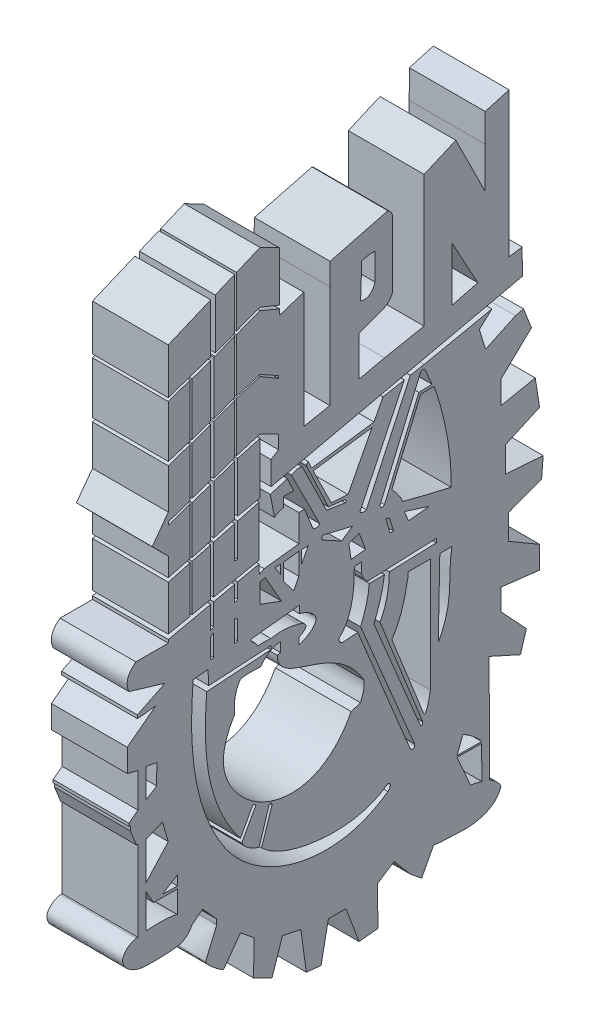
SolidWorks part; units mm, degrees
ref_plane "Alzado" through (0, 0, 0) normal (0, 0, 1) x (1, 0, 0)
ref_plane "Planta" through (0, 0, 0) normal (0, 1, 0) x (1, 0, 0)
ref_plane "Vista lateral" through (0, 0, 0) normal (1, 0, 0) x (0, 0, -1)
sketch "Croquis1" plane through (0, 0, 0) normal (1, 0, 0) x (0, 0, -1)
  line L0 (43.9363, 412.25) -> (43.9363, 221.2356)
  line L1 (43.9363, 221.2356) -> (23.5887, 211.0722)
  line L2 (23.5887, 211.0722) -> (23.5887, 208.8989)
  line L3 (16.8721, 195.9684) -> (35.5368, 210.1775)
  line L4 (23.9312, 137.0973) -> (23.9312, 156.5149)
  line L5 (23.9312, 179.1342) -> (23.9312, 197.7161)
  line L6 (16.8721, 195.9684) -> (16.8721, 180.9324)
  line L7 (16.8721, 180.9324) -> (23.9312, 179.1342)
  line L8 (23.9312, 179.1342) -> (23.9312, 156.5149)
  line L9 (23.9312, 156.5149) -> (17.9978, 151.9978)
  line L10 (17.9978, 151.9978) -> (17.9978, 150.0739)
  line L11 (17.9978, 150.0739) -> (18.9598, 150.0739)
  line L12 (18.9598, 150.0739) -> (18.9598, 147.1462)
  line L13 (18.9598, 147.1462) -> (22.9471, 137.0973)
  line L14 (22.9471, 137.0973) -> (23.9312, 137.0973)
  line L15 (23.9312, 137.0973) -> (23.9312, 83.8311)
  line L16 (23.9312, 83.8311) -> (22.9471, 83.8311)
  line L17 (56.0134, 68.3425) -> (75.8715, 68.3425)
  line L18 (75.8715, 68.3425) -> (75.8715, 65.2167)
  line L19 (263.3658, 283.0745) -> (283.4663, 271.8939)
  line L20 (263.3658, 283.0745) -> (263.3658, 267.8402)
  line L21 (263.3658, 267.8402) -> (285.9583, 272.3965)
  line L22 (285.9583, 272.3965) -> (309.7108, 262.7097)
  line L23 (309.7108, 262.7097) -> (310.5308, 247.9633)
  line L24 (310.5308, 247.9633) -> (288.8511, 254.1537)
  line L25 (288.8511, 254.1537) -> (285.9583, 272.3965)
  line L26 (287.5429, 272.8731) -> (285.9583, 272.3965)
  line L27 (288.8511, 254.1537) -> (266.2176, 243.9811)
  line L28 (266.2176, 243.9811) -> (266.2176, 227.2088)
  line L29 (266.2176, 227.2088) -> (291.2115, 225.4)
  line L30 (291.2115, 225.4) -> (291.2115, 235.5949)
  line L31 (291.2115, 235.5949) -> (266.2176, 243.9811)
  line L32 (291.2115, 235.5949) -> (310.5308, 247.9633)
  line L33 (268.337, 204.3163) -> (290.1487, 199.5858)
  line L34 (290.1487, 199.5858) -> (310.5308, 204.7917)
  line L35 (310.5308, 204.7917) -> (290.1487, 212.4724)
  line L36 (290.1487, 212.4724) -> (268.337, 204.3163)
  line L37 (290.1487, 212.4724) -> (291.2115, 225.4)
  line L38 (291.2115, 225.4) -> (310.5308, 218.9362)
  line L39 (310.5308, 218.9362) -> (310.5308, 204.7917)
  line L40 (268.337, 204.3163) -> (268.337, 187.8388)
  line L41 (268.337, 187.8388) -> (290.1487, 184.8338)
  line L42 (290.1487, 184.8338) -> (290.1487, 199.5858)
  line L43 (268.337, 187.8388) -> (288.8511, 175.8962)
  line L44 (288.8511, 175.8962) -> (309.7108, 172.2125)
  line L45 (309.7108, 172.2125) -> (290.1487, 184.8338)
  line L46 (288.8511, 175.8962) -> (288.8511, 161.1612)
  line L47 (288.8511, 161.1612) -> (309.7108, 159.5496)
  line L48 (309.7108, 159.5496) -> (309.7108, 172.2125)
  line L49 (263.3658, 164.1543) -> (288.8511, 161.1612)
  line L50 (263.3658, 164.1543) -> (263.3658, 150.0739)
  line L51 (263.3658, 150.0739) -> (283.4663, 148.3805)
  line L52 (283.4663, 148.3805) -> (285.0201, 161.6111)
  line L53 (263.3658, 150.0739) -> (280.1263, 132.1)
  line L54 (280.1263, 132.1) -> (299.2809, 130.6201)
  line L55 (299.2809, 130.6201) -> (283.4663, 148.3805)
  line L56 (280.1263, 132.1) -> (276.1921, 119.1503)
  line L57 (276.1921, 119.1503) -> (297.642, 119.1503)
  line L58 (297.642, 119.1503) -> (299.2809, 130.6201)
  line L59 (276.1921, 119.1503) -> (255.4875, 128.5526)
  line L60 (255.4875, 128.5526) -> (255.4875, 114.8521)
  line L61 (255.4875, 114.8521) -> (276.1921, 114.8521)
  line L62 (276.1921, 114.8521) -> (276.1921, 119.1503)
  line L63 (276.1921, 114.8521) -> (285.9583, 90.7476)
  line L64 (285.9583, 90.7476) -> (265.8398, 90.7476)
  line L65 (265.8398, 90.7476) -> (255.4875, 107.5904)
  line L66 (255.4875, 107.5904) -> (255.4875, 114.8521)
  line L67 (265.8398, 90.7476) -> (261.683, 78.6554)
  line L68 (261.683, 78.6554) -> (276.1921, 78.6554)
  line L69 (276.1921, 78.6554) -> (285.9583, 90.7476)
  line L70 (191.9441, 411.0372) -> (191.9441, 368.61)
  line L71 (183.7002, 361.1306) -> (169.7452, 356.0931)
  line L72 (169.7452, 356.0931) -> (186.6079, 346.5612)
  line L73 (169.7452, 356.0931) -> (169.7452, 329.7434)
  line L74 (169.7452, 329.7434) -> (186.5364, 333.5356)
  line L75 (233.601, 434.3151) -> (252.8256, 395.6782)
  line L76 (252.8256, 395.6782) -> (252.8256, 422.5142)
  line L77 (230.9785, 377.0491) -> (230.9785, 341.2878)
  line L78 (230.9785, 341.2878) -> (248.1079, 345.686)
  line L79 (248.1079, 345.686) -> (230.9785, 377.0491)
  line L80 (268.7154, 445.594) -> (268.7154, 350.1414)
  line L81 (268.7154, 350.1414) -> (277.3331, 351.5101)
  line L82 (276.1921, 317.421) -> (257.3854, 326.0513)
  line L83 (257.3854, 326.0513) -> (249.065, 318.4242)
  line L84 (249.065, 318.4242) -> (253.2252, 305.1547)
  line L85 (253.2252, 305.1547) -> (272.9115, 314.4257)
  line L86 (257.3854, 326.0513) -> (212.6544, 316.7428)
  line L87 (277.4757, 334.6795) -> (111.7206, 297.3389)
  line L88 (111.7206, 297.3389) -> (111.7206, 312.8594)
  line L89 (111.7206, 312.8594) -> (116.6334, 315.9908)
  line L90 (116.6334, 315.9908) -> (116.6334, 392.1998)
  line L91 (116.6334, 392.1998) -> (133.289, 397.6851)
  line L92 (133.289, 397.6851) -> (133.289, 320.9599)
  line L93 (133.289, 320.9599) -> (150.5326, 324.3307)
  line L94 (150.5326, 324.3307) -> (150.5326, 392.1998)
  line L95 (145.3173, 393.7699) -> (133.289, 397.6851)
  line L96 (261.683, 78.6554) -> (265.8398, 55.7232)
  line L97 (265.8398, 55.7232) -> (263.3658, 50.7772)
  line L98 (211.0187, 24.1224) -> (231.7393, 24.1224)
  line L99 (43.9363, 316.7428) -> (33.362, 302.302)
  line L100 (33.362, 302.302) -> (43.9363, 291.6046)
  line L101 (43.9363, 277.8816) -> (23.5887, 277.8816)
  line L102 (22.5389, 265.6648) -> (43.9363, 252.0848)
  line L103 (43.9363, 241.8738) -> (22.5389, 241.8738)
  line L104 (29.0853, 84.89) -> (29.0853, 199.5182)
  line L105 (29.0853, 199.5182) -> (39.1615, 209.0544)
  line L106 (39.1615, 209.0544) -> (50.0064, 197.5953)
  line L107 (50.0064, 197.5953) -> (50.0064, 83.8411)
  line L108 (54.1542, 81.4316) -> (54.1542, 197.5686)
  line L109 (54.1542, 197.5686) -> (42.739, 210.9483)
  line L110 (43.9363, 221.2356) -> (107.169, 252.7809)
  line L111 (107.169, 252.7809) -> (142.7909, 257.1439)
  line L113 (239.3484, 231.9879) -> (23.5887, 208.8989)
  line L114 (23.9312, 197.7161) -> (35.5368, 210.1775)
  line L115 (226.2809, 233.3335) -> (174.6192, 247.0102)
  line L116 (174.6192, 247.0102) -> (132.3561, 224.2069)
  line L117 (132.3561, 224.2069) -> (226.2809, 233.3335)
  line L118 (170.7616, 247.9633) -> (130.0415, 224.807)
  line L119 (130.0415, 224.807) -> (144.7007, 255.0685)
  line L120 (144.7007, 255.0685) -> (170.7616, 247.9633)
  line L121 (139.4645, 254.1537) -> (126.6124, 225.4)
  line L122 (126.6124, 225.4) -> (111.7206, 250.6964)
  line L123 (111.7206, 250.6964) -> (139.4645, 254.1537)
  line L124 (108.3015, 250.7703) -> (123.3251, 225.4)
  line L125 (85.7924, 238.6401) -> (123.3251, 225.4)
  line L126 (40.071, 215.5607) -> (80.3506, 236.3501)
  line L127 (80.3506, 236.3501) -> (119.9214, 222.7661)
  line L128 (119.9214, 222.7661) -> (40.071, 215.5607)
  line L129 (231.7393, 24.1224) -> (238.2993, 37.8143)
  line L130 (211.0187, 24.1224) -> (218.9341, 39.023)
  line L131 (88.9371, 431.138) -> (88.9371, 397.6851)
  line L132 (88.9371, 397.6851) -> (104.4667, 403.5146)
  line L133 (104.4667, 403.5146) -> (104.4667, 437.6562)
  line L134 (74.9479, 425.2664) -> (74.9479, 392.1998)
  line L135 (74.9479, 392.1998) -> (87.7057, 396.9888)
  line L136 (87.7057, 396.9888) -> (87.7057, 430.6212)
  line L137 (43.9363, 382.0604) -> (71.8987, 391.5214)
  line L138 (71.8987, 391.5214) -> (71.8987, 423.9866)
  line L139 (43.9363, 379.9088) -> (58.3682, 385.0332)
  line L140 (58.3682, 385.0332) -> (58.3682, 350.1414)
  line L141 (58.3682, 350.1414) -> (43.9363, 345.686)
  line L142 (59.607, 385.0332) -> (59.607, 350.1414)
  line L143 (59.607, 350.1414) -> (71.8987, 354.8191)
  line L144 (71.8987, 354.8191) -> (71.8987, 389.2227)
  line L145 (71.8987, 389.2227) -> (59.607, 385.0332)
  line L146 (74.9479, 390.2226) -> (87.7057, 395.6782)
  line L147 (87.7057, 395.6782) -> (87.7057, 360.389)
  line L148 (87.7057, 360.389) -> (73.9528, 354.8191)
  line L149 (73.9528, 354.8191) -> (73.9528, 390.2226)
  line L150 (73.9528, 390.2226) -> (74.9479, 390.2226)
  line L151 (88.9371, 395.6782) -> (104.4667, 401.5078)
  line L152 (104.4667, 401.5078) -> (104.4667, 365.1049)
  line L153 (104.4667, 365.1049) -> (88.9371, 360.389)
  line L154 (88.9371, 360.389) -> (88.9371, 395.6782)
  line L155 (43.9363, 343.2284) -> (58.3682, 348.139)
  line L156 (58.3682, 348.139) -> (58.3682, 315.9908)
  line L157 (58.3682, 315.9908) -> (43.9363, 311.0802)
  line L158 (59.607, 348.139) -> (59.607, 316.7428)
  line L159 (59.607, 316.7428) -> (71.8987, 320.9599)
  line L160 (71.8987, 320.9599) -> (71.8987, 351.5101)
  line L161 (71.8987, 352.9352) -> (59.607, 348.139)
  line L162 (71.8987, 351.5101) -> (71.8987, 352.9352)
  line L163 (73.9528, 353.5583) -> (87.7268, 358.6971)
  line L164 (87.7268, 358.6971) -> (87.7268, 326.0591)
  line L165 (87.7268, 326.0591) -> (73.9528, 320.9203)
  line L166 (73.9528, 320.9203) -> (73.9528, 353.5583)
  line L167 (88.9371, 359.2056) -> (104.4667, 363.9511)
  line L168 (104.4667, 363.9511) -> (104.4667, 331.1308)
  line L169 (104.4667, 331.1308) -> (88.9371, 326.3853)
  line L170 (88.9371, 326.3853) -> (88.9371, 359.2056)
  line L171 (43.9363, 309.2621) -> (58.3682, 314.4257)
  line L172 (58.3682, 314.4257) -> (58.3682, 283.0745)
  line L173 (58.3682, 283.0745) -> (43.9363, 279.2604)
  line L174 (59.607, 314.4257) -> (71.8987, 318.4242)
  line L175 (71.8987, 318.4242) -> (71.8987, 286.9367)
  line L176 (59.607, 282.9382) -> (71.8987, 286.2245)
  line L177 (59.607, 282.9382) -> (59.607, 314.4257)
  line L178 (73.9528, 318.4242) -> (73.9528, 286.9367)
  line L179 (71.8987, 286.2245) -> (71.8987, 286.9367)
  line L180 (87.7268, 291.6118) -> (87.7268, 322.0786)
  line L181 (73.9528, 318.4242) -> (73.9528, 319.2123)
  line L182 (89.7282, 324.5491) -> (104.4667, 328.6171)
  line L183 (104.4667, 328.6171) -> (104.4667, 294.5937)
  line L184 (104.4667, 294.5937) -> (89.7282, 291.6118)
  line L185 (89.7282, 291.6118) -> (89.7282, 324.5491)
  line L186 (73.9528, 319.2123) -> (87.7268, 323.8874)
  line L187 (87.7268, 323.8874) -> (87.7268, 322.0786)
  line L188 (73.9528, 286.9367) -> (87.7268, 290.9366)
  line L189 (87.7268, 290.9366) -> (87.7268, 291.6118)
  line L190 (43.9363, 276.7135) -> (58.3682, 280.5166)
  line L191 (58.3682, 280.5166) -> (58.3682, 250.7703)
  line L192 (59.607, 280.8431) -> (59.607, 250.2453)
  line L193 (71.8987, 284.0822) -> (71.8987, 252.783)
  line L194 (73.9161, 284.6138) -> (73.9161, 253.1994)
  line L195 (87.7268, 288.2533) -> (87.7268, 266.9268)
  line L196 (87.7268, 266.9268) -> (89.7282, 266.9268)
  line L197 (89.7282, 266.9268) -> (89.7282, 288.7807)
  line L198 (89.7282, 288.7807) -> (103.8958, 292.5142)
  line L199 (73.9161, 284.6138) -> (87.7268, 288.2533)
  line L200 (59.607, 280.8431) -> (71.8987, 284.0822)
  line L201 (43.9363, 247.0102) -> (58.3682, 249.9896)
  line L202 (103.8958, 259.3887) -> (103.8958, 292.5142)
  line L203 (73.9161, 253.1994) -> (103.8958, 259.3887)
  line L204 (58.3682, 250.7703) -> (58.3682, 249.9896)
  line L205 (59.607, 250.2453) -> (71.8987, 252.783)
  line L206 (43.9363, 243.9811) -> (71.8987, 250.1196)
  line L207 (71.8987, 250.1196) -> (71.8987, 235.1854)
  line L208 (73.9161, 250.5625) -> (73.9161, 236.1918)
  line L209 (87.7268, 253.5944) -> (87.7268, 243.0816)
  line L210 (89.7282, 254.0337) -> (89.7282, 244.0801)
  line L211 (89.7282, 254.0337) -> (103.8958, 257.1439)
  line L212 (73.9161, 250.5625) -> (87.7268, 253.5944)
  line L213 (114.2618, 249.7709) -> (117.9329, 244.0801)
  line L214 (117.9329, 244.0801) -> (117.9329, 250.1196)
  line L215 (117.9329, 250.1196) -> (114.2618, 249.7709)
  line L216 (119.9214, 250.1196) -> (130.0415, 251.3807)
  line L217 (130.0415, 251.3807) -> (130.0415, 237.048)
  line L218 (130.0415, 237.048) -> (126.6124, 230.4015)
  line L219 (126.6124, 230.4015) -> (119.9214, 239.2883)
  line L220 (119.9214, 239.2883) -> (119.9214, 250.1196)
  line L221 (131.8859, 251.3807) -> (136.2774, 251.3807)
  line L222 (136.2774, 251.3807) -> (131.8859, 243.0816)
  line L223 (131.8859, 243.0816) -> (131.8859, 251.3807)
  line L224 (71.8987, 231.9879) -> (71.8987, 218.4327)
  line L225 (73.9161, 233.0291) -> (73.9161, 218.6148)
  line L226 (87.7268, 233.818) -> (87.7268, 219.861)
  line L227 (89.7282, 233.131) -> (89.7282, 220.0416)
  line L228 (145.3173, 252.7809) -> (145.3173, 250.1196)
  line L229 (145.3173, 250.1196) -> (158.2073, 243.0816)
  line L230 (158.2073, 243.0816) -> (165.4522, 247.9633)
  line L231 (165.4522, 247.9633) -> (145.3173, 252.7809)
  line L232 (163.0364, 239.2883) -> (169.7452, 241.8738)
  line L233 (169.7452, 241.8738) -> (174.1664, 230.4015)
  line L234 (174.1664, 230.4015) -> (164.4859, 229.4093)
  line L235 (164.4859, 229.4093) -> (163.0364, 239.2883)
  line L236 (220.6941, 213.355) -> (220.6941, 210.7982)
  line L237 (220.6941, 210.7982) -> (189.7708, 209.748)
  line L238 (183.5235, 184.1455) -> (211.6828, 113.2795)
  line L239 (212.6544, 116.8748) -> (191.3534, 170.1599)
  line L240 (223.0228, 203.5582) -> (230.9785, 203.5582)
  line L241 (216.77, 200.5213) -> (216.77, 128.5526)
  line L242 (216.77, 200.5213) -> (216.77, 203.5582)
  line L243 (216.77, 203.5582) -> (202.0039, 203.5582)
  line L244 (202.0039, 203.5582) -> (202.0039, 200.5213)
  line L245 (223.0228, 203.5582) -> (221.9912, 152.8582)
  spline S0 degree 3 poles (22.9471, 83.8311) (19.2347, 83.6756) (13.3804, 79.0493) (14.3398, 69.9272) (21.2783, 66.0681) (29.6539, 64.546) (53.7403, 65.0523) (54.0322, 67.3359) (56.0134, 68.3425) knots 0 0 0 0 0.182088 0.2261 0.496742 0.557462 0.772579 1 1 1 1
  spline S1 degree 3 poles (75.8715, 65.2167) (75.7324, 63.7271) (71.8626, 56.1185) (69.0831, 49.2329) (67.7913, 45.7368) (77.8952, 38.3773) (80.3506, 37.1752) knots 0 0 0 0 0.597773 0.693632 0.735053 1 1 1 1
  spline S2 degree 1 poles (43.9363, 412.25) (104.4667, 437.6562) knots 0 0 1 1
  spline S3 degree 1 poles (104.4667, 437.6562) (145.6538, 416.4816) knots 0 0 1 1
  spline S4 degree 1 poles (145.6538, 416.4816) (145.3173, 393.7699) knots 0 0 1 1
  spline S5 degree 1 poles (145.3173, 393.7699) (150.5326, 392.1998) knots 0 0 1 1
  spline S6 degree 1 poles (150.5326, 392.1998) (150.6897, 406.6305) knots 0 0 1 1
  spline S7 degree 1 poles (150.6897, 406.6305) (188.7781, 416.4816) knots 0 0 1 1
  spline S8 degree 1 poles (188.7781, 416.4816) (208.7397, 405.4302) knots 0 0 1 1
  spline S9 degree 1 poles (208.7397, 405.4302) (208.8847, 361.1306) knots 0 0 1 1
  spline S10 degree 2 poles (208.8847, 361.1306) (201.2606, 348.0995) (186.6079, 346.5612) knots 0 0 0 1 1 1
  spline S11 degree 1 poles (186.6079, 346.5612) (186.5364, 333.5356) knots 0 0 1 1
  spline S12 degree 1 poles (186.5364, 333.5356) (212.6544, 338.6067) knots 0 0 1 1
  spline S13 degree 1 poles (212.6544, 338.6067) (212.6883, 425.2664) knots 0 0 1 1
  spline S14 degree 1 poles (212.6883, 425.2664) (233.601, 434.3151) knots 0 0 1 1
  spline S15 degree 1 poles (233.601, 434.3151) (252.8256, 422.5142) knots 0 0 1 1
  spline S16 degree 2 poles (23.5887, 277.8816) (20.6152, 272.0241) (22.5389, 265.6648) knots 0 0 0 1 1 1
  spline S17 degree 1 poles (252.8256, 422.5142) (252.9657, 441.0734) knots 0 0 1 1
  spline S18 degree 1 poles (252.9657, 441.0734) (268.7154, 445.594) knots 0 0 1 1
  spline S19 degree 1 poles (268.7154, 445.594) (287.3763, 433.6324) knots 0 0 1 1
  spline S20 degree 1 poles (287.3763, 433.6324) (287.5429, 345.686) knots 0 0 1 1
  spline S21 degree 1 poles (287.5429, 345.686) (297.5942, 338.6067) knots 0 0 1 1
  spline S22 degree 1 poles (297.5942, 338.6067) (297.642, 322.4637) knots 0 0 1 1
  spline S23 degree 1 poles (297.642, 322.4637) (276.1921, 317.421) knots 0 0 1 1
  spline S24 degree 1 poles (276.1921, 317.421) (272.9115, 314.4257) knots 0 0 1 1
  spline S25 degree 1 poles (272.9115, 314.4257) (278.1889, 315.7094) knots 0 0 1 1
  spline S26 degree 1 poles (278.1889, 315.7094) (283.4663, 302.302) knots 0 0 1 1
  spline S27 degree 1 poles (283.4663, 302.302) (305.289, 291.6046) knots 0 0 1 1
  spline S28 degree 1 poles (278.1889, 315.7094) (300.4395, 305.1547) knots 0 0 1 1
  spline S29 degree 1 poles (300.4395, 305.1547) (305.289, 291.6046) knots 0 0 1 1
  spline S30 degree 1 poles (277.3331, 351.5101) (277.4757, 334.6795) knots 0 0 1 1
  spline S31 degree 1 poles (277.4757, 334.6795) (297.642, 322.4637) knots 0 0 1 1
  spline S32 degree 1 poles (277.3331, 351.5101) (287.5429, 345.686) knots 0 0 1 1
  spline S33 degree 1 poles (283.4663, 302.302) (263.3658, 283.0745) knots 0 0 1 1
  spline S34 degree 1 poles (305.289, 291.6046) (287.5429, 272.8731) knots 0 0 1 1
  spline S35 degree 2 poles (188.7781, 416.4816) (191.8661, 414.5474) (191.9441, 411.0372) knots 0 0 0 1 1 1
  spline S36 degree 2 poles (191.9441, 368.61) (189.8169, 362.9706) (183.7002, 361.1306) knots 0 0 0 1 1 1
  spline S37 degree 2 poles (22.5389, 241.8738) (14.2242, 235.7793) (17.9978, 227.2088) knots 0 0 0 1 1 1
  spline S38 degree 1 poles (17.9978, 227.2088) (41.6864, 220.1118) knots 0 0 1 1
  spline S39 degree 1 poles (108.3015, 250.7703) (85.7924, 238.6401) knots 0 0 1 1
  spline S40 degree 1 poles (171.5383, 396.5308) (170.7616, 373.7786) knots 0 0 1 1
  spline S41 degree 1 poles (180.3799, 397.6851) (180.3799, 379.9088) knots 0 0 1 1
  spline S42 degree 2 poles (171.5383, 396.5308) (175.2223, 397.7159) (180.3799, 397.6851) knots 0 0 0 1 1 1
  spline S43 degree 2 poles (170.7616, 373.7786) (177.4327, 371.9515) (180.3799, 379.9088) knots 0 0 0 1 1 1
  spline S44 degree 1 poles (80.3506, 37.1752) (91.5252, 52.5778) knots 0 0 1 1
  spline S45 degree 1 poles (91.5252, 52.5778) (100.5968, 45.3651) knots 0 0 1 1
  spline S46 degree 1 poles (100.5968, 45.3651) (100.1325, 22.5345) knots 0 0 1 1
  spline S47 degree 1 poles (100.1325, 22.5345) (112.368, 16.5573) knots 0 0 1 1
  spline S48 degree 1 poles (250.6259, 45.3651) (255.9424, 48.4483) knots 0 0 1 1
  spline S49 degree 1 poles (112.368, 16.5573) (119.2574, 37.1693) knots 0 0 1 1
  spline S50 degree 1 poles (119.2574, 37.1693) (131.376, 34.6523) knots 0 0 1 1
  spline S51 degree 1 poles (131.376, 34.6523) (134.9432, 8.4052) knots 0 0 1 1
  spline S52 degree 1 poles (134.9432, 8.4052) (144.7007, 7.3621) knots 0 0 1 1
  spline S53 degree 1 poles (144.7007, 7.3621) (149.5454, 31.6408) knots 0 0 1 1
  spline S54 degree 1 poles (149.5454, 31.6408) (161.1653, 31.5963) knots 0 0 1 1
  spline S55 degree 1 poles (161.1653, 31.5963) (169.7452, 8.5201) knots 0 0 1 1
  spline S56 degree 1 poles (169.7452, 8.5201) (182.2725, 9.8027) knots 0 0 1 1
  spline S57 degree 1 poles (182.2725, 9.8027) (181.7957, 35.4223) knots 0 0 1 1
  spline S58 degree 1 poles (80.3506, 37.1752) (100.4302, 37.1693) knots 0 0 1 1
  spline S59 degree 2 poles (144.7007, 7.3621) (156.8673, 8.5882) (168.885, 10.8337) knots 0 0 0 1 1 1
  spline S60 degree 2 poles (112.368, 16.5573) (122.8527, 18.4414) (133.289, 20.577) knots 0 0 0 1 1 1
  spline S61 degree 1 poles (203.5823, 30.1266) (202.8849, 13.8268) knots 0 0 1 1
  spline S62 degree 1 poles (182.2725, 9.8027) (202.8849, 13.8268) knots 0 0 1 1
  spline S63 degree 1 poles (181.7957, 35.4223) (192.9033, 42.6539) knots 0 0 1 1
  spline S64 degree 1 poles (192.9033, 42.6539) (203.5823, 30.1266) knots 0 0 1 1
  spline S65 degree 1 poles (181.7957, 35.4223) (197.0288, 37.8143) knots 0 0 1 1
  spline S66 degree 1 poles (234.3483, 82.5133) (238.2993, 92.5989) knots 0 0 1 1
  spline S67 degree 2 poles (238.2993, 92.5989) (245.9312, 88.4138) (250.6232, 82.3833) knots 0 0 0 1 1 1
  spline S68 degree 1 poles (234.3483, 82.5133) (250.6232, 82.3833) knots 0 0 1 1
  spline S69 degree 1 poles (234.3483, 81.4316) (250.6232, 81.2616) knots 0 0 1 1
  spline S70 degree 1 poles (250.6232, 81.2616) (250.7453, 59.4748) knots 0 0 1 1
  spline S71 degree 1 poles (234.3483, 81.4316) (243.3418, 61.0612) knots 0 0 1 1
  spline S72 degree 2 poles (243.3418, 61.0612) (245.0406, 61.0705) (250.7453, 59.4748) knots 0 0 0 1 1 1
  spline S73 degree 1 poles (236.7087, 230.4015) (255.4875, 204.3163) knots 0 0 1 1
  spline S74 degree 1 poles (236.7087, 230.4015) (223.0228, 213.355) knots 0 0 1 1
  spline S75 degree 1 poles (227.2077, 210.7981) (236.7087, 224.2069) knots 0 0 1 1
  spline S76 degree 1 poles (236.7087, 224.2069) (250.6232, 204.3163) knots 0 0 1 1
  spline S77 degree 1 poles (255.9424, 48.4483) (255.4875, 204.3163) knots 0 0 1 1
  spline S78 degree 1 poles (250.6232, 204.3163) (250.6232, 82.3833) knots 0 0 1 1
  spline S79 degree 1 poles (250.7453, 59.4748) (250.6259, 45.3651) knots 0 0 1 1
  spline S80 degree 3 poles (263.3658, 50.7772) (261.0214, 40.898) (245.5751, 37.1144) (227.4744, 38.7613) (210.8017, 37.0616) (202.0411, 49.0078) knots 0 0 0 0 0.378429 0.478429 1 1 1 1
  spline S81 degree 3 poles (202.0411, 49.0078) (209.1053, 63.6071) (229.8427, 62.2632) (243.3418, 61.0612) knots 0 0 0 0 1 1 1 1
  spline S82 degree 2 poles (263.3658, 50.7772) (261.033, 54.8352) (255.9151, 57.7966) knots 0 0 0 1 1 1
  spline S83 degree 1 poles (265.8398, 55.7232) (257.9432, 56.5035) knots 0 0 1 1
  spline S84 degree 1 poles (75.8715, 68.3425) (66.5887, 78.6554) knots 0 0 1 1
  spline S85 degree 1 poles (66.5887, 78.6554) (59.607, 73.0706) knots 0 0 1 1
  spline S86 degree 2 poles (56.0134, 68.3425) (57.9512, 70.2153) (59.607, 73.0706) knots 0 0 0 1 1 1
  spline S87 degree 3 poles (50.0064, 83.8411) (46.163, 85.7401) (31.3756, 85.2008) (29.0853, 84.89) knots 0 0 0 0 1 1 1 1
  spline S88 degree 3 poles (54.1542, 81.4316) (56.0457, 80.2436) (59.3877, 77.5333) (60.1423, 74.5126) (59.607, 73.0706) knots 0 0 0 0 0.648368 1 1 1 1
  spline S89 degree 2 poles (50.0064, 83.8411) (52.2719, 82.8454) (54.1542, 81.4316) knots 0 0 0 1 1 1
  spline S90 degree 1 poles (203.5823, 30.1266) (211.0187, 24.1224) knots 0 0 1 1
  spline S91 degree 2 poles (227.2077, 210.7981) (223.6549, 210.1533) (223.0228, 213.355) knots 0 0 0 1 1 1
  spline S92 degree 2 poles (189.7708, 209.748) (189.5691, 194.4562) (183.5235, 184.1455) knots 0 0 0 1 1 1
  spline S93 degree 2 poles (191.3534, 170.1599) (198.4821, 179.9637) (202.0039, 200.5213) knots 0 0 0 1 1 1
  spline S94 degree 2 poles (216.77, 128.5526) (215.0399, 117.629) (212.6544, 116.8748) knots 0 0 0 1 1 1
  spline S95 degree 3 poles (230.9785, 203.5582) (227.6586, 184.8298) (233.1643, 174.8399) (221.9912, 152.8582) knots 0 0 0 0 1 1 1 1
  spline S96 degree 1 poles (29.0853, 178.8682) (36.3671, 177.4442) knots 0 0 1 1
  spline S97 degree 1 poles (36.2696, 164.1543) (36.3671, 177.4442) knots 0 0 1 1
  spline S98 degree 1 poles (29.0853, 159.5496) (36.2696, 164.1543) knots 0 0 1 1
  spline S99 degree 1 poles (29.0853, 137.0973) (40.071, 141.7004) knots 0 0 1 1
  spline S100 degree 1 poles (40.071, 141.7004) (43.9363, 128.5526) knots 0 0 1 1
  spline S101 degree 1 poles (29.0853, 112.2087) (43.9363, 128.5526) knots 0 0 1 1
  spline S102 degree 1 poles (29.0853, 107.5904) (34.2514, 98.6171) knots 0 0 1 1
  spline S103 degree 1 poles (34.2514, 98.6171) (50.0064, 98.4809) knots 0 0 1 1
  spline S104 degree 1 poles (40.071, 100.3917) (50.0064, 100.204) knots 0 0 1 1
  spline S105 degree 1 poles (40.071, 100.3917) (50.0064, 106.5864) knots 0 0 1 1
  spline S106 degree 1 poles (104.4667, 363.9511) (116.6334, 356.7256) knots 0 0 1 1
  spline S107 degree 1 poles (104.4667, 365.1049) (116.6334, 358.38) knots 0 0 1 1
  spline S108 degree 1 poles (104.4667, 328.6171) (116.6334, 323.348) knots 0 0 1 1
  spline S109 degree 1 poles (104.4667, 331.1308) (116.6334, 325.0383) knots 0 0 1 1
  spline S110 degree 1 poles (117.1453, 431.138) (117.2716, 398.3073) knots 0 0 1 1
  spline S111 degree 1 poles (118.6143, 397.6851) (118.6124, 430.3838) knots 0 0 1 1
  spline S112 degree 1 poles (117.2716, 398.3073) (104.4667, 403.5146) knots 0 0 1 1
  spline S113 degree 1 poles (125.6626, 426.7592) (125.6128, 395.157) knots 0 0 1 1
  spline S114 degree 1 poles (127.1954, 395.6782) (126.883, 426.1318) knots 0 0 1 1
  spline S115 degree 2 poles (117.2443, 396.1946) (117.2197, 394.2897) (117.195, 392.3847) knots 0.356717 0.356717 0.356717 1 1 1
  spline S116 degree 1 poles (104.4667, 401.5078) (117.2443, 396.1946) knots 0 0 1 1
  spline S117 degree 1 poles (118.6143, 397.6851) (125.6128, 395.157) knots 0 0 1 1
  spline S118 degree 1 poles (119.2574, 395.6782) (119.2788, 393.071) knots 0 0 1 1
  spline S119 degree 1 poles (119.2574, 395.6782) (123.3251, 394.4036) knots 0 0 1 1
  spline S120 degree 1 poles (133.289, 397.6851) (133.2321, 422.8677) knots 0 0 1 1
  spline S121 degree 1 poles (134.2902, 397.3592) (134.6559, 422.1357) knots 0 0 1 1
  spline S122 degree 1 poles (176.5058, 209.748) (186.5364, 209.748) knots 0 0 1 1
  spline S123 degree 3 poles (186.5364, 209.748) (185.2332, 201.2585) (183.477, 194.7338) (179.6104, 184.8338) knots 0 0 0 0 1 1 1 1
  spline S124 degree 1 poles (179.6104, 184.8338) (210.3512, 111.4048) knots 0 0 1 1
  spline S125 degree 2 poles (210.3512, 111.4048) (212.0418, 111.0715) (211.6828, 113.2795) knots 0 0 0 1 1 1
  spline S126 degree 2 poles (176.5058, 209.748) (175.9367, 200.3541) (170.7616, 187.8388) knots 0 0 0 1 1 1
  spline S127 degree 1 poles (170.7616, 187.8388) (206.3999, 103.1307) knots 0 0 1 1
  spline S128 degree 1 poles (168.885, 185.6115) (203.5823, 101.561) knots 0 0 1 1
  spline S129 degree 2 poles (203.5823, 101.561) (206.5721, 99.2679) (206.3999, 103.1307) knots 0 0 0 1 1 1
  spline S130 degree 1 poles (168.885, 185.6115) (158.487, 184.8338) knots 0 0 1 1
  spline S131 degree 2 poles (158.487, 184.8338) (155.9478, 186.3632) (156.4921, 188.4378) knots 0 0 0 1 1 1
  spline S132 degree 1 poles (171.4527, 224.7222) (171.528, 217.6135) knots 0 0 1 1
  spline S133 degree 2 poles (171.528, 217.6135) (172.0861, 214.3741) (175.4622, 211.5067) knots 0 0 0 1 1 1
  spline S134 degree 1 poles (175.4622, 211.5067) (220.6941, 213.355) knots 0 0 1 1
  spline S135 degree 2 poles (166.6215, 224.2052) (167.1974, 197.8595) (156.4921, 188.4378) knots 0 0 0 1 1 1
  spline S136 degree 1 poles (70.1302, 213.8795) (70.5879, 204.3163) knots 0 0 1 1
  spline S137 degree 1 poles (70.5879, 204.3163) (111.7206, 206.6597) knots 0 0 1 1
  spline S138 degree 1 poles (111.7206, 206.6597) (111.5619, 204.3163) knots 0 0 1 1
  spline S139 degree 1 poles (69.2505, 201.5326) (111.5619, 204.3163) knots 0 0 1 1
  spline S140 degree 3 poles (69.2505, 201.5326) (66.6778, 167.2405) (68.6408, 136.6507) (91.5252, 106.5864) knots 0 0 0 0 1 1 1 1
  spline S141 degree 1 poles (91.5252, 106.5864) (99.6821, 121.5934) knots 0 0 1 1
  spline S142 degree 1 poles (101.6615, 120.4182) (92.3214, 103.5319) knots 0 0 1 1
  spline S143 degree 1 poles (103.8958, 95.3671) (110.4448, 116.4595) knots 0 0 1 1
  spline S144 degree 1 poles (112.368, 115.3461) (105.4965, 94.2537) knots 0 0 1 1
  spline S145 degree 2 poles (99.6821, 121.5934) (101.5154, 121.3449) (101.6615, 120.4182) knots 0 0 0 1 1 1
  spline S146 degree 2 poles (110.4448, 116.4595) (112.2472, 117.4062) (112.368, 115.3461) knots 0 0 0 1 1 1
  spline S147 degree 2 poles (92.3214, 103.5319) (95.7934, 97.624) (103.8958, 95.3671) knots 0 0 0 1 1 1
  spline S148 degree 3 poles (105.4965, 94.2537) (115.1759, 84.2316) (153.4841, 74.9429) (180.548, 82.8488) (188.7781, 89.3418) knots 0 0 0 0 0.556818 1 1 1 1
  spline S149 degree 3 poles (60.3226, 212.8299) (56.7667, 169.884) (63.6966, 133.8003) (92.8452, 87.4217) (134.7166, 65.2422) (175.1467, 75.0619) (188.7781, 84.731) knots 0 0 0 0 0.417407 0.504329 0.828671 1 1 1 1
  spline S150 degree 3 poles (188.7781, 89.3418) (191.2673, 88.4378) (190.5798, 86.5119) (188.7781, 84.731) knots 0 0 0 0 1 1 1 1
  spline S151 degree 2 poles (212.6544, 316.7428) (208.1183, 315.9131) (203.5823, 315.0834) knots 0 0 0 0.335008 0.335008 0.335008
  spline S152 degree 1 poles (170.298, 253.5944) (199.5943, 314.354) knots 0 0 1 1
  spline S153 degree 1 poles (174.6192, 252.7809) (203.5823, 315.0834) knots 0 0 1 1
  spline S154 degree 2 poles (199.5943, 314.354) (192.5841, 313.0717) (185.574, 311.7894) knots 0.482272 0.482272 0.482272 1 1 1
  spline S155 degree 2 poles (170.298, 253.5944) (171.8921, 251.6932) (174.6192, 252.7809) knots 0 0 0 1 1 1
  spline S156 degree 1 poles (183.5235, 250.6964) (210.3512, 313.5462) knots 0 0 1 1
  spline S157 degree 1 poles (213.2653, 313.5462) (217.9177, 302.7385) knots 0 0 1 1
  spline S158 degree 2 poles (210.3512, 313.5462) (211.979, 314.8938) (213.2653, 313.5462) knots 0 0 0 1 1 1
  spline S159 degree 1 poles (186.5364, 249.7709) (209.1838, 302.55) knots 0 0 1 1
  spline S160 degree 1 poles (209.1838, 302.55) (217.9177, 302.7385) knots 0 0 1 1
  spline S161 degree 2 poles (183.5235, 250.6964) (184.3281, 247.8169) (186.5364, 249.7709) knots 0 0 0 1 1 1
  spline S162 degree 2 poles (142.7909, 257.1439) (192.5823, 246.6557) (239.3484, 231.9879) knots 0 0 0 1 1 1
  spline S163 degree 1 poles (191.3534, 255.7937) (210.3512, 300.7317) knots 0 0 1 1
  spline S164 degree 2 poles (210.3512, 300.7317) (214.515, 301.2211) (219.3504, 300.8716) knots 0 0 0 1 1 1
  spline S165 degree 2 poles (219.3504, 300.8716) (230.7643, 267.6053) (230.5362, 237.6788) knots 0 0 0 1 1 1
  spline S166 degree 2 poles (230.5362, 237.6788) (214.8732, 241.1265) (198.5287, 245.5179) knots 0 0 0 1 1 1
  spline S167 degree 2 poles (191.3534, 255.7937) (196.4542, 250.7826) (198.5287, 245.5179) knots 0 0 0 1 1 1
  spline S168 degree 2 poles (185.574, 311.7894) (182.5922, 306.0681) (179.6104, 300.3467) knots 0 0 0 0.258233 0.258233 0.258233
  spline S169 degree 1 poles (151.4371, 268.2797) (162.4802, 267.4779) knots 0 0 1 1
  spline S170 degree 1 poles (151.4371, 268.2797) (139.4645, 292.5142) knots 0 0 1 1
  spline S171 degree 1 poles (139.4645, 292.5142) (178.3218, 297.8742) knots 0 0 1 1
  spline S172 degree 2 poles (138.5068, 294.5937) (137.3921, 297.014) (136.2774, 299.4343) knots 0.300498 0.300498 0.300498 1 1 1
  spline S173 degree 1 poles (138.5068, 294.5937) (179.6104, 300.3467) knots 0 0 1 1
  spline S174 degree 1 poles (135.2666, 297.3389) (149.5454, 266.9268) knots 0 0 1 1
  spline S175 degree 2 poles (178.3218, 297.8742) (170.401, 282.676) (162.4802, 267.4779) knots 0.314033 0.314033 0.314033 1 1 1
  spline S176 degree 2 poles (135.2666, 297.3389) (134.8709, 298.9614) (136.2774, 299.4343) knots 0 0 0 1 1 1
  spline S177 degree 1 poles (149.5454, 266.9268) (160.646, 265.6648) knots 0 0 1 1
  spline S178 degree 1 poles (160.646, 263.6734) (148.2848, 265.6648) knots 0 0 1 1
  spline S179 degree 2 poles (160.646, 265.6648) (161.6808, 264.4505) (160.646, 263.6734) knots 0 0 0 1 1 1
  spline S180 degree 1 poles (148.2848, 265.6648) (132.2045, 298.5896) knots 0 0 1 1
  spline S181 degree 1 poles (125.1289, 297.3549) (143.705, 260.3251) knots 0 0 1 1
  spline S182 degree 2 poles (125.1289, 297.3549) (128.6002, 299.4305) (132.2045, 298.5896) knots 0 0 0 1 1 1
  spline S183 degree 1 poles (139.4645, 259.3887) (133.7481, 273.5697) knots 0 0 1 1
  spline S184 degree 2 poles (139.4645, 259.3887) (142.7359, 258.0202) (143.705, 260.3251) knots 0 0 0 1 1 1
  spline S185 degree 1 poles (126.6124, 287.6019) (122.4438, 296.5664) knots 0 0 1 1
  spline S186 degree 3 poles (133.7481, 273.5697) (134.6475, 277.0234) (134.0077, 279.966) (129.6202, 281.3957) knots 0 0 0 0 1 1 1 1
  spline S187 degree 1 poles (129.6202, 281.3957) (129.5018, 287.553) knots 0 0 1 1
  spline S188 degree 1 poles (129.5018, 287.553) (126.6124, 287.6019) knots 0 0 1 1
  spline S189 degree 1 poles (111.2157, 293.2267) (122.4438, 296.5664) knots 0 0 1 1
  spline S190 degree 1 poles (111.2157, 293.2267) (114.0368, 278.603) knots 0 0 1 1
  spline S191 degree 3 poles (114.0368, 278.603) (112.7115, 275.711) (113.4743, 273.6565) (118.0188, 271.6302) knots 0 0 0 0 1 1 1 1
  spline S192 degree 1 poles (118.0188, 271.6302) (117.9329, 254.0993) knots 0 0 1 1
  spline S193 degree 1 poles (103.8958, 257.1439) (103.941, 251.1705) knots 0 0 1 1
  spline S194 degree 3 poles (117.9329, 199.5182) (117.1917, 199.3838) (116.463, 199.2344) (115.7467, 199.0707) knots 0 0 0 0 0.008373 0.008373 0.008373 0.008373
  spline S195 degree 1 poles (170.7616, 144.4387) (164.5466, 142.5224) knots 0 0 1 1
  spline S196 degree 3 poles (123.5245, 115.595) (121.4978, 106.7933) (132.3283, 97.4577) (153.7747, 88.6528) (174.076, 90.0415) (187.4659, 93.9612) knots 0 0 0 0 0.353731 0.453731 1 1 1 1
  spline S197 degree 3 poles (119.4484, 115.9794) (117.1912, 103.2761) (125.8406, 95.3426) (150.6422, 86.2859) (169.6957, 84.2379) (188.3736, 91.2183) knots 0 0 0 0 0.485354 0.585354 1 1 1 1
  spline S198 degree 1 poles (170.7616, 144.4387) (188.3736, 91.2183) knots 0 0 1 1
  spline S199 degree 1 poles (218.9341, 128.5526) (222.4386, 136.2854) knots 0 0 1 1
  spline S200 degree 1 poles (218.9341, 128.5526) (217.9177, 60.4829) knots 0 0 1 1
  spline S201 degree 2 poles (87.7268, 179.3345) (86.4283, 189.9376) (91.5252, 197.5686) knots 0 0 0 1 1 1
  spline S202 degree 1 poles (221.9912, 61.2227) (222.4386, 136.2854) knots 0 0 1 1
  spline S203 degree 1 poles (117.9329, 199.5182) (118.1001, 208.3766) knots 0 0 1 1
  spline S204 degree 1 poles (130.0415, 205.496) (130.1836, 197.5686) knots 0 0 1 1
  spline S205 degree 3 poles (130.1836, 197.5686) (151.3093, 192.2877) (160.7778, 182.4528) (161.8208, 170.1599) knots 0 0 0 0 1 1 1 1
  spline S206 degree 2 poles (118.1001, 208.3766) (126.0252, 208.6862) (130.0415, 205.496) knots 0 0 0 1 1 1
  spline S207 degree 3 poles (102.6524, 193.854) (101.6111, 183.771) (128.2373, 169.3173) (152.2651, 164.8259) (165.4522, 148.3805) knots 0 0 0 0 0.28609 1 1 1 1
  spline S208 degree 3 poles (115.7467, 199.0707) (115.9913, 189.1187) (145.2634, 180.6988) (163.3153, 172.7604) (172.875, 156.5149) knots 0 0 0 0 0.341113 1 1 1 1
  spline S209 degree 3 poles (172.875, 156.5149) (173.932, 151.8964) (171.8478, 148.1377) (170.7616, 144.4387) knots 0 0 0 0 1 1 1 1
  spline S210 degree 1 poles (165.4522, 148.3805) (164.5466, 142.5224) knots 0 0 1 1
  spline S211 degree 1 poles (104.4667, 246.4866) (104.4677, 233.818) knots 0 0 1 1
  spline S212 degree 1 poles (104.4677, 233.818) (118.6143, 228.5633) knots 0 0 1 1
  spline S213 degree 1 poles (118.6143, 228.5633) (107.877, 247.3881) knots 0 0 1 1
  spline S214 degree 1 poles (104.4667, 246.4866) (107.877, 247.3881) knots 0 0 1 1
  spline S215 degree 1 poles (199.5943, 239.2883) (202.4332, 232.5634) knots 0 0 1 1
  spline S216 degree 1 poles (202.4332, 232.5634) (215.9725, 233.9556) knots 0 0 1 1
  spline S217 degree 1 poles (215.9725, 233.9556) (199.5943, 239.2883) knots 0 0 1 1
  spline S218 degree 1 poles (187.4659, 241.3159) (190.1606, 231.6593) knots 0 0 1 1
  spline S219 degree 1 poles (189.7708, 240.4476) (192.5287, 231.6593) knots 0 0 1 1
  spline S220 degree 1 poles (187.4659, 241.3159) (189.7708, 240.4476) knots 0 0 1 1
  spline S221 degree 1 poles (190.1606, 231.6593) (192.5287, 231.6593) knots 0 0 1 1
  spline S222 degree 3 poles (102.6524, 193.854) (89.0269, 185.7083) (80.6828, 168.1706) (79.6819, 146.4312) (89.3793, 129.7519) (121.3301, 110.6688) (150.2106, 114.7114) (164.5466, 142.5224) knots 0.066109 0.066109 0.066109 0.066109 0.272847 0.326121 0.568552 0.638971 1 1 1 1
  spline S223 degree 3 poles (118.0524, 205.8492) (114.3729, 205.924) (106.7692, 203.2552) (102.6524, 193.854) knots 0 0 0 0 1 1 1 1
  spline S224 degree 2 poles (130.1032, 202.0538) (139.2987, 206.8332) (130.0415, 209.748) knots 0 0 0 1 1 1
  spline S225 degree 3 poles (130.1836, 197.5686) (136.1635, 199.8857) (140.7635, 203.1468) (141.8753, 209.5756) (136.9029, 213.737) (130.371, 215.5607) knots 0 0 0 0 0.484081 0.584081 1 1 1 1
  spline S226 degree 1 poles (130.371, 215.5607) (130.5599, 220.3462) knots 0 0 1 1
  spline S227 degree 1 poles (126.6124, 287.6019) (119.9214, 287.7242) knots 0 0 1 1
  spline S228 degree 1 poles (119.9214, 287.7242) (120.0492, 281.3957) knots 0 0 1 1
  spline S229 degree 2 poles (120.0492, 281.3957) (124.8936, 282.2132) (129.6202, 281.3957) knots 0 0 0 1 1 1
  spline S230 degree 3 poles (120.0492, 281.3957) (117.7053, 280.9504) (115.1721, 279.8656) (114.0368, 278.603) knots 0 0 0 0 1 1 1 1
  spline S231 degree 3 poles (118.0188, 271.6302) (119.5587, 273.165) (122.5042, 273.3158) (128.4158, 273.3902) (132.6102, 273.5089) (133.7481, 273.5697) knots 0 0 0 0 0.468546 0.568546 1 1 1 1
  spline S232 degree 1 poles (130.0415, 273.4447) (130.0415, 255.5823) knots 0 0 1 1
  spline S233 degree 3 poles (111.7206, 210.6295) (108.9037, 211.0892) (105.7528, 211.1192) (102.6524, 210.7982) knots 0.467168 0.467168 0.467168 0.467168 1 1 1 1
  spline S234 degree 3 poles (102.6524, 210.7982) (102.483, 213.7076) (98.2126, 214.2868) (98.3543, 216.8998) knots 0 0 0 0 1 1 1 1
  spline S235 degree 2 poles (111.7206, 218.3301) (121.3202, 217.4466) (130.371, 215.5607) knots 0 0 0 1 1 1
  spline S236 degree 1 poles (118.131, 217.6205) (118.1863, 219.0221) knots 0 0 1 1
  spline S237 degree 2 poles (130.0415, 209.748) (120.7108, 212.6191) (111.7206, 210.6295) knots 0 0 0 1 1 1
  spline S238 degree 2 poles (91.5252, 197.5686) (95.7779, 198.6575) (104.8417, 197.8305) knots 0 0 0 1 1 1
  spline S239 degree 1 poles (261.683, 78.6554) (255.8467, 81.2616) knots 0 0 1 1
  spline S240 degree 1 poles (118.0188, 298.7578) (117.9203, 295.2209) knots 0 0 1 1
  spline S241 degree 1 poles (104.4667, 294.5937) (111.2157, 293.2267) knots 0 0 1 1
  spline S242 degree 1 poles (103.8958, 259.3887) (117.9479, 257.1439) knots 0 0 1 1
sketch "Croquis2" plane through (0, 0, 0) normal (1, 0, 0) x (0, 0, -1)
  line L1 (-64.8575, 498.4601) -> (370.8093, 498.4601)
  line L2 (-64.8575, 498.4601) -> (-64.8575, -31.6011)
  line L3 (-64.8575, -31.6011) -> (370.8093, -31.6011)
  line L4 (370.8093, 498.4601) -> (370.8093, -31.6011)
extrude "Saliente-Extruir1" add sketch "Croquis1" along normal blind 50
